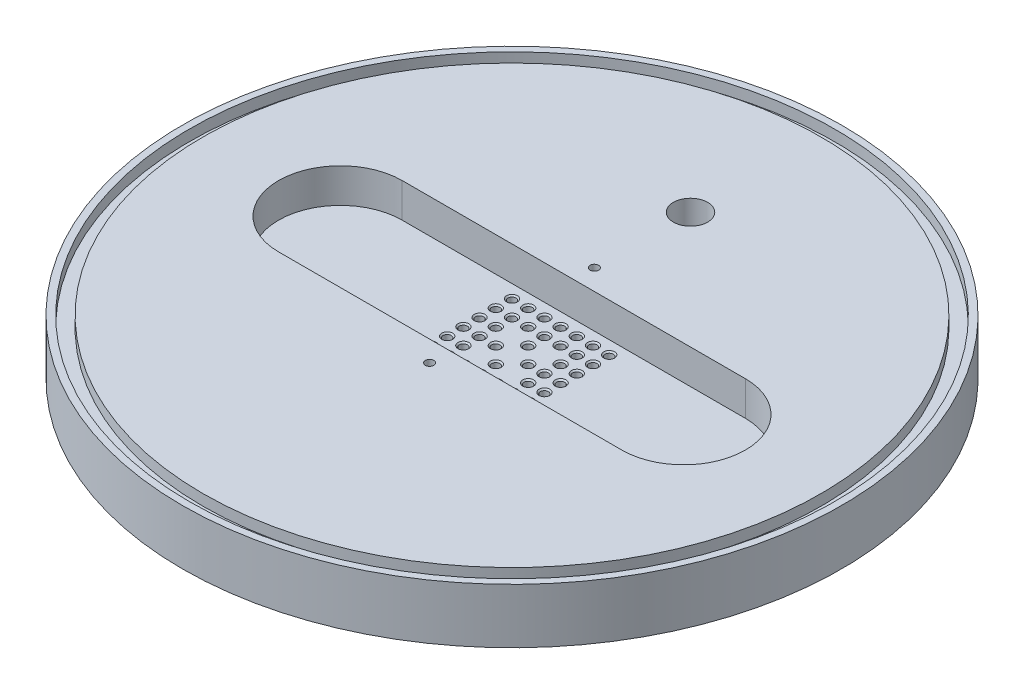
SolidWorks part; units mm, degrees
ref_plane "Front Plane" through (0, 0, 0) normal (0, 0, 1) x (1, 0, 0)
ref_plane "Top Plane" through (0, 0, 0) normal (0, 1, 0) x (1, 0, 0)
ref_plane "Right Plane" through (0, 0, 0) normal (1, 0, 0) x (0, 0, -1)
ref_axis "Axial" through (0, 0.508, 0) along (0, -1, 0)
ref_plane "Bottom Plane" through (0, -10.16, 0) normal (0, 1, 0) x (1, 0, 0)
sketch "Sketch1" plane through (0, 0, 0) normal (0, 1, 0) x (1, 0, 0)
  circle A0 centre (0, 0) radius 60.96
  dimension "D1" = 121.92
extrude "Billet" add sketch "Sketch1" against normal blind 10.16
sketch "Sketch2" plane through (0, 0, 0) normal (0, 1, 0) x (1, 0, 0)
  line L0 (-71.6435, 0) -> (78.9532, 0) construction
  line L1 (-31.75, 11.43) -> (31.75, 11.43)
  line L2 (-31.75, -11.43) -> (31.75, -11.43)
  line L3 (0, 44.5081) -> (0, -98.5298) construction
  arc A4 (-31.75, 11.43) -> (-31.75, -11.43) centre (-31.75, 0) ccw
  arc A5 (31.75, -11.43) -> (31.75, 11.43) centre (31.75, 0) ccw
  dimension "D1" = 22.86
  dimension "D2" = 31.75
extrude "Kerosene Well" cut sketch "Sketch2" against normal blind 6.35
sketch "Sketch4" plane through (0, -10.16, 0) normal (0, 1, 0) x (1, 0, 0)
  line L0 (0, 37.2675) -> (0, -28.2573) construction
  line L1 (-38.2015, 0) -> (37.6086, 0) construction
  circle A0 centre (8.9916, 8.9916) radius 0.7493
  dimension "D1" = 1.4986
  dimension "D2" = 8.9916
  dimension "D3" = 8.9916
extrude "First Kerosene Outlet" cut sketch "Sketch4" along normal up to next
chamfer "Bottom Needle Chamfer" distance 0.254 angle 45 1 edges at (8.9916, -6.35, -8.2423)
pattern_linear "LPattern1" count 7 spacing 2.9972 along (0, 0, 1) count 7 spacing 2.9972 along (-1, 0, 0) skipping (2, 2), (2, 4), (3, 3), (4, 2), (4, 4) of "First Kerosene Outlet", "Bottom Needle Chamfer"
sketch "Sketch13" plane through (0, 0, 0) normal (0, 1, 0) x (1, 0, 0)
  line L0 (0, 67.9606) -> (0, -66.9336) construction
  line L1 (-21.7094, 0) -> (16.1787, 0) construction
  circle A0 centre (0, 15.24) radius 0.7937
  circle A1 centre (0, -15.24) radius 0.7937
  dimension "D1" = 1.5875
  dimension "D2" = 15.24
extrude "Dowel Holes" cut sketch "Sketch13" against normal blind 3.175
sketch "Sketch14" plane through (0, 0, 0) normal (0, 1, 0) x (1, 0, 0)
  line L0 (0, 62.0498) -> (0, -64.4455) construction
  circle A0 centre (0, 33.02) radius 3.175
  dimension "D1" = 6.35
  dimension "D2" = 33.02
extrude "Manifold Hole" cut sketch "Sketch14" against normal up to next
sketch "Sketch15" plane through (0, -10.16, 0) normal (0, 1, 0) x (1, 0, 0)
  circle A0 centre (0, 0) radius 57.15
  circle A1 centre (0, 0) radius 59.69
  dimension "D1" = 114.3
  dimension "D2" = 119.38
extrude "Chamber O Ring" cut sketch "Sketch15" along normal blind 2.032
sketch "Sketch16" plane through (0, 0, 0) normal (0, 1, 0) x (1, 0, 0)
  circle A0 centre (0, 0) radius 59.69
  circle A1 centre (0, 0) radius 57.15
  dimension "D1" = 119.38
  dimension "D2" = 114.3
extrude "Top O ring" cut sketch "Sketch16" against normal blind 2.032
